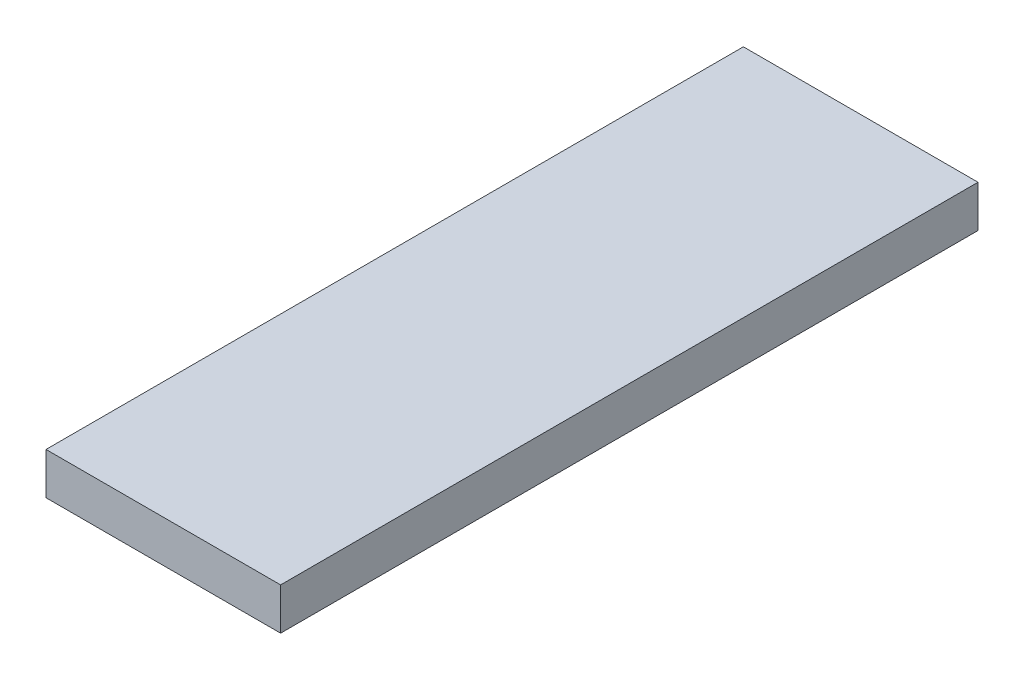
SolidWorks part; units mm, degrees
ref_plane "Front Plane" through (0, 0, 0) normal (0, 0, 1) x (1, 0, 0)
ref_plane "Top Plane" through (0, 0, 0) normal (0, 1, 0) x (1, 0, 0)
ref_plane "Right Plane" through (0, 0, 0) normal (1, 0, 0) x (0, 0, -1)
sketch "Sketch1" plane through (0, 0, 0) normal (0, 1, 0) x (1, 0, 0)
  line L0 (0, 0) -> (16.82, 0)
  line L1 (16.82, 0) -> (16.82, 50)
  line L2 (16.82, 50) -> (0, 50)
  line L3 (0, 50) -> (0, 0)
  dimension "D1" = 50
  dimension "D2" = 16.82
extrude "Boss-Extrude1" add sketch "Sketch1" along normal blind 3
